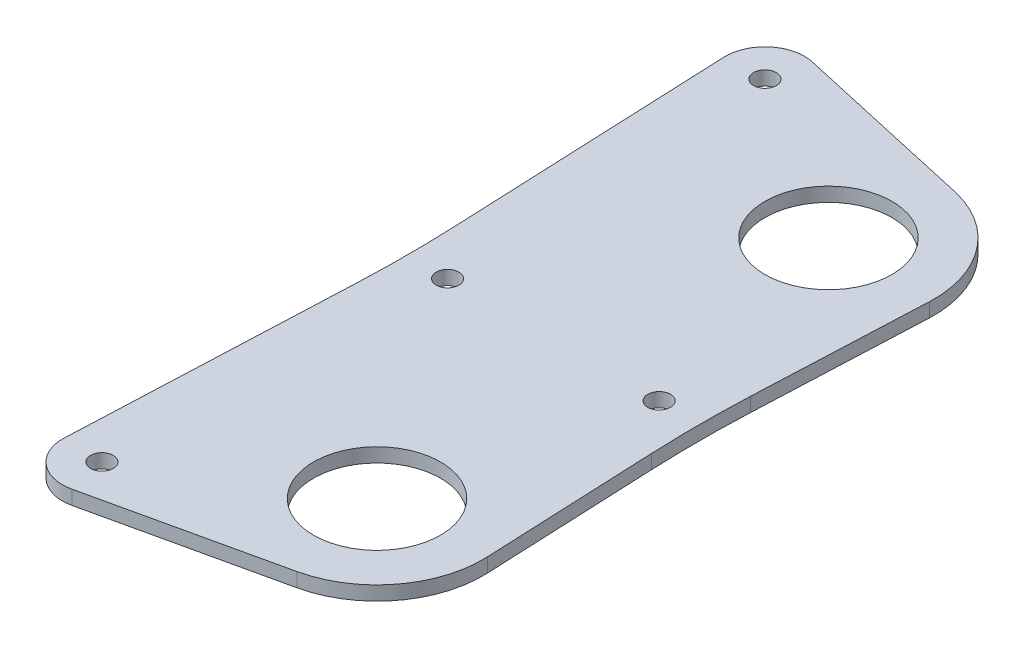
SolidWorks part; units mm, degrees
material "6061-T6 (SS)"
ref_plane "Front" through (0, 0, 0) normal (0, 0, 1) x (1, 0, 0)
ref_plane "Top" through (0, 0, 0) normal (0, 1, 0) x (1, 0, 0)
ref_plane "Right" through (0, 0, 0) normal (1, 0, 0) x (0, 0, -1)
sketch "Sketch1" plane through (0, 0, 0) normal (0, 1, 0) x (1, 0, 0)
  line L0 (0, 50.8) -> (0, -50.8) construction
  line L4 (-50.8, 88.9) -> (38.1, 88.9)
  line L5 (-50.8, 88.9) -> (-50.8, -88.9)
  line L6 (-50.8, -88.9) -> (38.1, -88.9)
  line L7 (38.1, 88.9) -> (38.1, -88.9)
  circle A0 centre (0, 50.8) radius 14.2875
  circle A1 centre (0, -50.8) radius 14.2875
  circle A4 centre (0, 50.8) radius 38.1 construction
  circle A5 centre (0, -50.8) radius 38.1 construction
  point P4 (0, 0)
  dimension "D2" = 28.575
  dimension "D3" = 50.8
  dimension "D4" = 76.2
  dimension "D1" = 101.6
extrude "Boss-Extrude1" add sketch "Sketch1" along normal blind 3.175
hole_wizard "#10 Clearance Hole1" positions "Sketch2" profile "Sketch3" hole size "#10" standard "ANSI Inch"
sketch "Sketch2" plane through (0, 3.175, 0) normal (0, 1, 0) x (1, 0, 0)
  line L6 (0, 50.8) -> (0, -50.8) construction
  line L9 (-38.1, 74.6125) -> (-38.1, -74.6125) construction
  point P2 (12.7, 0)
  point P4 (-38.1, 74.6125)
  point P10 (-38.1, -74.6125)
  point P40 (-34.925, 0)
  point P51 (-38.1, 0)
  dimension "D1" = 12.7
  dimension "D2" = 34.925
  dimension "D3" = 38.1
  dimension "D4" = 149.225
sketch "Sketch3" plane through (12.7, 3.175, 0) normal (1, 0, 0) x (0, 0, 1)
  line L0 (0, 0) -> (0, 4.7088)
  line L1 (0, 4.7088) -> (2.5527, 3.175)
  line L2 (2.5527, 3.175) -> (2.5527, 0)
  line L5 (2.5527, 0) -> (0, 0)
  line L10 (0, 4.7088) -> (-2.5527, 3.175) construction
  line L11 (0, -6.35) -> (0, 107.95) construction
  dimension "Hole Dia." = 5.1054
  dimension "Hole Depth" = 3.175
  dimension "Drill Angle" = 118
sketch "Sketch4" plane through (0, 3.175, 0) normal (0, 1, 0) x (1, 0, 0)
  line L0 (5.2044, 74.0368) -> (-36.1543, 83.3)
  line L1 (-46.9947, 74.234) -> (-44.2953, 10.7987)
  line L2 (-46.9947, -74.234) -> (-44.2953, -10.7987)
  line L3 (-36.1543, -83.3) -> (5.2044, -74.0368)
  line L4 (23.7897, 49.7585) -> (22.0976, 11.1098)
  line L5 (23.7897, -49.7585) -> (22.0976, -11.1098)
  circle A0 centre (0, 50.8) radius 23.8125 construction
  circle A1 centre (-38.1, 74.6125) radius 8.9027 construction
  circle A2 centre (-34.925, 0) radius 8.9027 construction
  circle A3 centre (12.7, 0) radius 8.9027 construction
  circle A4 centre (-38.1, -74.6125) radius 8.9027 construction
  circle A5 centre (0, -50.8) radius 23.8125 construction
  circle A6 centre (-38.1, 74.6125) radius 2.5527 construction
  circle A7 centre (0, 50.8) radius 14.2875 construction
  arc A8 (5.2044, 74.0368) -> (23.7897, 49.7585) centre (0, 50.8) cw
  arc A9 (-46.9947, 74.234) -> (-36.1543, 83.3) centre (-38.1, 74.6125) cw
  arc A10 (-36.1543, -83.3) -> (-46.9947, -74.234) centre (-38.1, -74.6125) cw
  arc A11 (5.2044, -74.0368) -> (23.7897, -49.7585) centre (0, -50.8) ccw
  arc A12 (22.0976, -11.1098) -> (22.0976, 11.1098) centre (275.8545, 0) cw
  arc A13 (-44.2953, -10.7987) -> (-44.2953, 10.7987) centre (-298.0656, 0) ccw
  point P27 (23.789, 49.7412)
  point P33 (-36.0993, 83.2877)
  dimension "D1" = 6.35
  dimension "D2" = 9.525
  dimension "D3" = 254
extrude "Cut-Extrude1" cut sketch "Sketch4" against normal through all flip side to cut
